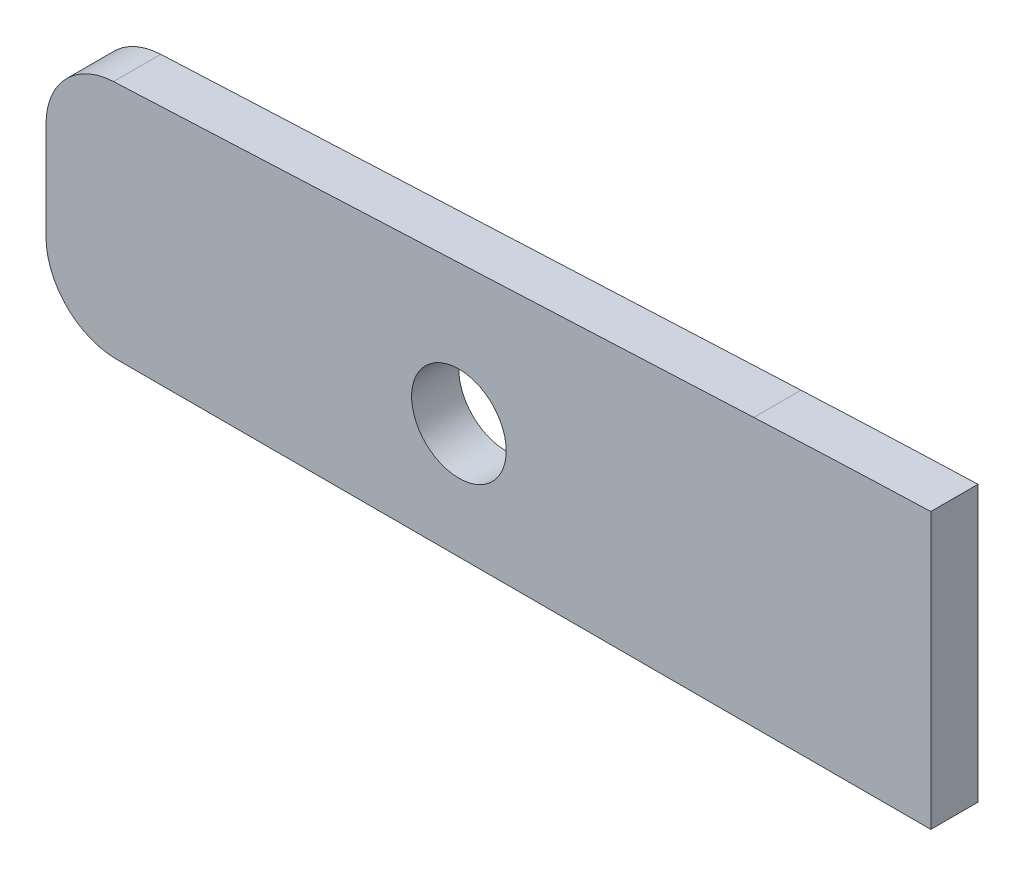
SolidWorks part; units mm, degrees
ref_plane "前视基准面" through (0, 0, 0) normal (0, 0, 1) x (1, 0, 0)
ref_plane "上视基准面" through (0, 0, 0) normal (0, 1, 0) x (1, 0, 0)
ref_plane "右视基准面" through (0, 0, 0) normal (1, 0, 0) x (0, 0, -1)
sketch "草图1" plane through (0, 0, 0) normal (0, 0, 1) x (1, 0, 0)
  line L0 (0, 81.9069) -> (0, 12) construction
  line L1 (0, 16.5) -> (84.8038, 16.5)
  line L2 (84.8038, 16.5) -> (90, 13.5)
  line L3 (0, -16.5) -> (60, -16.5)
  line L4 (60, -16.5) -> (67.7942, -12)
  line L5 (67.7942, -12) -> (116.5359, -12)
  line L6 (116.5359, -12) -> (120, -14)
  line L7 (0, 16.5) -> (0, 12)
  line L8 (-48.3677, 0) -> (26.6044, 0) construction
  line L9 (720, 53.6929) -> (726.0954, 58.7056)
  line L10 (726.0954, 58.7056) -> (770, 66)
  line L11 (770, 66) -> (770, 52)
  line L12 (90, 13.5) -> (0, 13.5) construction
  line L13 (720, 53.6929) -> (770, 62) construction
  line L14 (120, -14) -> (0, -14) construction
  line L15 (120, -14) -> (0, -17) construction
  line L16 (0, 12) -> (-40, 12)
  line L17 (0, -12) -> (-149, -12)
  line L21 (0, -12) -> (0, -16.5)
  line L22 (0, 12) -> (0, 0) construction
  line L23 (0, -12) -> (0, -75.7106) construction
  line L24 (-95, 10.7433) -> (-149.274, 8.2618)
  line L26 (-155, 2.2681) -> (-155, -6)
  line L27 (-80, -12) -> (-80, 11.3355)
  arc A0 (90, 13.5) -> (300, 15.3376) centre (90, 12013.5) ccw
  arc A1 (120, -14) -> (370, -4.6196) centre (-129.9219, 9982.8765) ccw
  arc A2 (300, 15.3376) -> (720, 53.6929) centre (249.7935, 2883.8437) ccw
  arc A3 (370, -4.6196) -> (770, 52) centre (258.3915, 2225.107) ccw
  arc A4 (-4, 0) -> (-160, -4) centre (-4, -3044) ccw construction
  circle A8 centre (-40.0007, -0.2129) radius 4.01
  circle A9 centre (-120, -2.2111) radius 4.01
  arc A10 (-149, -12) -> (-155, -6) centre (-149, -6) cw
  arc A11 (-40, 12) -> (-95, 10.7433) centre (-40, -1192.1843) ccw
  arc A12 (-149.274, 8.2618) -> (-155, 2.2681) centre (-149, 2.2681) ccw
  point P40 (-155, 8)
  dimension "D1" = 770
  dimension "D3" = 300
  dimension "D16" = 52
  dimension "D17" = 50
  dimension "D19" = 12000
  dimension "D20" = 10000
  dimension "D22" = 4
  dimension "D24" = 4
  dimension "D29" = 60
  dimension "D30" = 8.02
  dimension "D32" = 8.02
  dimension "D23" = 40
  dimension "D33" = 6
  dimension "D2" = 33
  dimension "D4" = 400
  dimension "D5" = 30
  dimension "D6" = 30
  dimension "D7" = 30
  dimension "D8" = 30
  dimension "D9" = 14
  dimension "D10" = 120
  dimension "D11" = 90
  dimension "D12" = 3
  dimension "D13" = 5
  dimension "D14" = 2
  dimension "D15" = 60
  dimension "D18" = 10
  dimension "D21" = 3
  dimension "D25" = 155
  dimension "D26" = 4
  dimension "D27" = 160
  dimension "D28" = 24
  dimension "D31" = 40
  dimension "D34" = 40.0007
  dimension "D35" = 75
extrude "凸台-拉伸1" add sketch "草图1" along normal mid plane 4 contours L24 A12 L26 A10 L17 L27 A11 A9 region at (-116.0613, -1.0765, 0)
